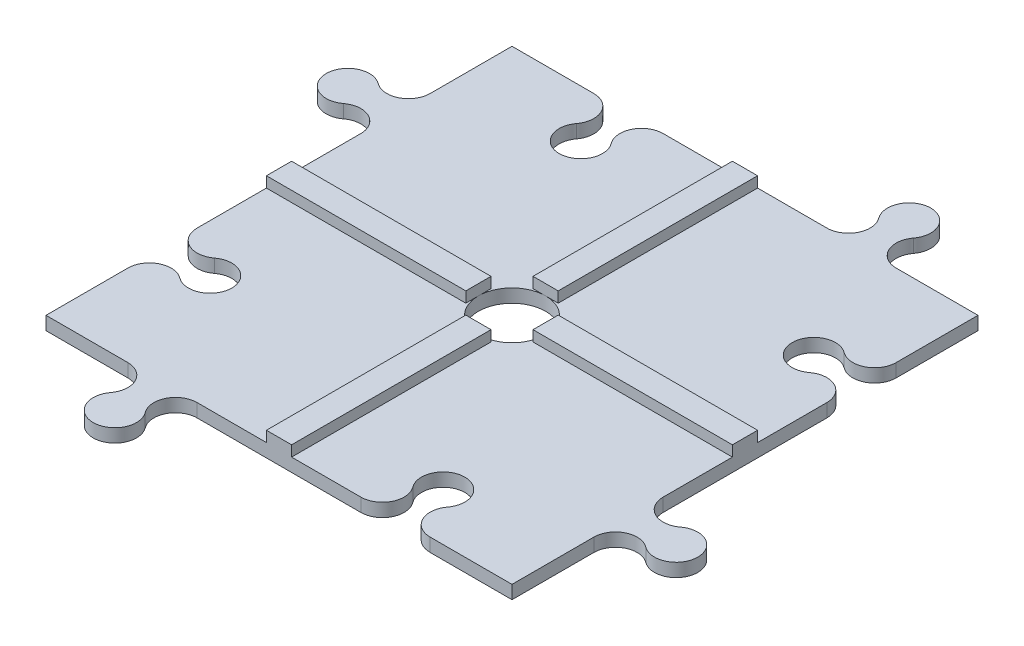
SolidWorks part; units mm, degrees
note: The reader was unsure of these and kept them because the rebuilt part matched: shared geometry of "Sketch2<3>".
ref_plane "Front Plane" through (0, 0, 0) normal (0, 0, 1) x (1, 0, 0)
ref_plane "Top Plane" through (0, 0, 0) normal (0, 1, 0) x (1, 0, 0)
ref_plane "Right Plane" through (0, 0, 0) normal (1, 0, 0) x (0, 0, -1)
sketch "Sketch1" plane through (0, 0, 0) normal (0, 1, 0) x (1, 0, 0)
  line L1 (55.5, -55.5) -> (-55.5, -55.5)
  line L2 (55.5, -55.5) -> (55.5, 55.5)
  line L3 (55.5, 55.5) -> (-55.5, 55.5)
  line L4 (-55.5, -55.5) -> (-55.5, 55.5)
  line L5 (55.5, -55.5) -> (-55.5, 55.5) construction
  line L6 (55.5, 55.5) -> (-55.5, -55.5) construction
  circle A0 centre (0, 0) radius 55.5 construction
  circle A1 centre (0, 0) radius 55.5 construction
  dimension "D1" = 111
extrude "Boss-Extrude1" add sketch "Sketch1" along normal blind 3.175 contours L4 L3 L2 L1
sketch "Sketch2" plane through (0, 0, 0) normal (0, 1, 0) x (1, 0, 0)
  line L0 (-55.5, 27.75) -> (-113.1129, 27.75) construction
  line L1 (-55.5, 36.005) -> (-55.5, 19.495)
  line L2 (-55.5, -55.5) -> (-55.5, 55.5) construction
  line L3 (0, 0) -> (-55.5, 0) construction
  line L4 (55.5, 55.5) -> (-55.5, -55.5) construction
  line L5 (-55.5, -36.005) -> (-55.5, -19.495)
  arc A0 (-63.755, 23.6225) -> (-72.01, 27.75) centre (-66.8506, 27.75) cw
  arc A1 (-63.755, 23.6225) -> (-55.5, 19.495) centre (-60.6594, 19.495) cw
  arc A2 (-63.755, 31.8775) -> (-55.5, 36.005) centre (-60.6594, 36.005) ccw
  arc A3 (-63.755, -23.6225) -> (-55.5, -19.495) centre (-60.6594, -19.495) ccw construction
  arc A4 (-63.755, 31.8775) -> (-72.01, 27.75) centre (-66.8506, 27.75) ccw
  arc A5 (-63.755, -23.6225) -> (-72.01, -27.75) centre (-66.8506, -27.75) ccw construction
  arc A6 (-63.755, -31.8775) -> (-72.01, -27.75) centre (-66.8506, -27.75) cw construction
  arc A7 (-63.755, -31.8775) -> (-55.5, -36.005) centre (-60.6594, -36.005) cw construction
  arc A8 (-47.245, -31.8775) -> (-55.5, -36.005) centre (-50.3406, -36.005) ccw
  arc A9 (-47.245, -31.8775) -> (-38.99, -27.75) centre (-44.1494, -27.75) ccw
  arc A10 (-47.245, -23.6225) -> (-38.99, -27.75) centre (-44.1494, -27.75) cw
  arc A11 (-47.245, -23.6225) -> (-55.5, -19.495) centre (-50.3406, -19.495) cw
  point P19 (-77.1865, 19.495)
  point P22 (-77.1865, 36.005)
  dimension "D1" = 16.51
  dimension "D2" = 16.51
extrude "Boss-Extrude2" add sketch "Sketch2" along normal up to surface (3.175 mm away) contours A0 A4 A2 L1 A1 up to face at (0, 3.175, 0)
extrude "Cut-Extrude2" cut sketch "Sketch2<3>" along normal through all contours L5 A11 A10 A9 A8
sketch "Sketch2<3>" plane through (0, 0, 0) normal (0, 1, 0) x (1, 0, 0) same geometry as "Sketch2"
sketch "Sketch3" [suppressed] plane through (0, 0, 0) normal (0, 0, 1) x (1, 0, 0)
  line L0 (0, 0) -> (0, 29.4045) construction
  line L1 (55.5, 0) -> (-55.5, 0) construction
pattern_circular "CirPattern1" count 4 over 360 about axis through (0, 0, 0) along (0, 1, 0) of "Boss-Extrude2", "Cut-Extrude2"
sketch "Sketch4" plane through (0, 3.175, 0) normal (0, 1, 0) x (1, 0, 0)
  circle A0 centre (0, 0) radius 8.001
  dimension "D1" = 16.002
extrude "Cut-Extrude3" cut sketch "Sketch4" against normal up to surface (3.175 mm away) up to face at (0, 0, 0)
sketch "Sketch5" plane through (0, 3.175, 0) normal (0, 1, 0) x (1, 0, 0)
  line L0 (-55.5, 3) -> (-7.4173, 3)
  line L1 (-55.5, -3) -> (-7.4173, -3)
  line L2 (-55.5, 55.5) -> (-55.5, -55.5)
  line L3 (-36.005, -55.5) -> (-55.5, -55.5) construction
  line L4 (-55.5, 0) -> (-8.001, 0) construction
  line L5 (-8.001, 3) -> (-8.001, -3)
  circle A0 centre (0, 0) radius 8.001 construction
  line M27 (-55.5, 19.495) -> (-55.5, -19.495)
  dimension "D1" = 6
extrude "Boss-Extrude3" add sketch "Sketch5" along normal blind 2.54 contours L4 L2 L1 L5 | L4 L5 L0 M27
pattern_circular "CirPattern2" count 4 over 360 about axis through (0, 0, 0) along (0, 1, 0) of "Boss-Extrude3"
sketch "Sketch6" plane through (0, 3.175, 0) normal (0, 1, 0) x (1, 0, 0)
  line L0 (0, 8.001) -> (-3, 8.001) construction
  line L1 (-3, 8.001) -> (-3, 55.5) construction
  line L2 (-3, 55.5) -> (-19.495, 55.5) construction
  line L3 (-36.005, 55.5) -> (-55.5, 55.5) construction
  line L4 (-55.5, 55.5) -> (-55.5, 36.005) construction
  line L5 (-55.5, 19.495) -> (-55.5, 3) construction
  line L6 (-55.5, 3) -> (-8.001, 3) construction
  line L7 (-8.001, 3) -> (-8.001, 0) construction
  line L8 (19.495, 55.5) -> (3, 55.5) construction
  line L9 (3, 55.5) -> (3, 8.001) construction
  line L10 (3, 8.001) -> (0, 8.001) construction
  line L11 (8.001, 0) -> (8.001, 3) construction
  line L12 (8.001, 3) -> (55.5, 3) construction
  line L13 (55.5, 3) -> (55.5, 19.495) construction
  line L14 (55.5, 36.005) -> (55.5, 55.5) construction
  line L15 (55.5, 55.5) -> (36.005, 55.5) construction
  line L16 (55.5, -19.495) -> (55.5, -3) construction
  line L17 (55.5, -3) -> (8.001, -3) construction
  line L18 (8.001, -3) -> (8.001, 0) construction
  line L19 (0, -8.001) -> (3, -8.001) construction
  line L20 (3, -8.001) -> (3, -55.5) construction
  line L21 (3, -55.5) -> (19.495, -55.5) construction
  line L22 (36.005, -55.5) -> (55.5, -55.5) construction
  line L23 (55.5, -55.5) -> (55.5, -36.005) construction
  line L24 (-19.495, -55.5) -> (-3, -55.5) construction
  line L25 (-3, -55.5) -> (-3, -8.001) construction
  line L26 (-3, -8.001) -> (0, -8.001) construction
  line L27 (-8.001, 0) -> (-8.001, -3) construction
  line L28 (-8.001, -3) -> (-55.5, -3) construction
  line L29 (-55.5, -3) -> (-55.5, -19.495) construction
  line L30 (-55.5, -36.005) -> (-55.5, -55.5) construction
  line L31 (-55.5, -55.5) -> (-36.005, -55.5) construction
  line L32 (0, 8.001) -> (-3, 8.001)
  line L33 (-3, 8.001) -> (-3, 55.5)
  line L34 (-3, 55.5) -> (-19.495, 55.5)
  line L35 (-36.005, 55.5) -> (-55.5, 55.5)
  line L36 (-55.5, 55.5) -> (-55.5, 36.005)
  line L37 (-55.5, 19.495) -> (-55.5, 3)
  line L38 (-55.5, 3) -> (-8.001, 3)
  line L39 (-8.001, 3) -> (-8.001, 0)
  line L40 (19.495, 55.5) -> (3, 55.5)
  line L41 (3, 55.5) -> (3, 8.001)
  line L42 (3, 8.001) -> (0, 8.001)
  line L43 (8.001, 0) -> (8.001, 3)
  line L44 (8.001, 3) -> (55.5, 3)
  line L45 (55.5, 3) -> (55.5, 19.495)
  line L46 (55.5, 36.005) -> (55.5, 55.5)
  line L47 (55.5, 55.5) -> (36.005, 55.5)
  line L48 (55.5, -19.495) -> (55.5, -3)
  line L49 (55.5, -3) -> (8.001, -3)
  line L50 (8.001, -3) -> (8.001, 0)
  line L51 (0, -8.001) -> (3, -8.001)
  line L52 (3, -8.001) -> (3, -55.5)
  line L53 (3, -55.5) -> (19.495, -55.5)
  line L54 (36.005, -55.5) -> (55.5, -55.5)
  line L55 (55.5, -55.5) -> (55.5, -36.005)
  line L56 (-19.495, -55.5) -> (-3, -55.5)
  line L57 (-3, -55.5) -> (-3, -8.001)
  line L58 (-3, -8.001) -> (0, -8.001)
  line L59 (-8.001, 0) -> (-8.001, -3)
  line L60 (-8.001, -3) -> (-55.5, -3)
  line L61 (-55.5, -3) -> (-55.5, -19.495)
  line L62 (-55.5, -36.005) -> (-55.5, -55.5)
  line L63 (-55.5, -55.5) -> (-36.005, -55.5)
  arc A1 (-19.495, 55.5) -> (-23.6225, 47.245) centre (-19.495, 50.3406) ccw construction
  arc A2 (-31.8775, 47.245) -> (-23.6225, 47.245) centre (-27.75, 44.1494) ccw construction
  arc A3 (-31.8775, 47.245) -> (-36.005, 55.5) centre (-36.005, 50.3406) ccw construction
  arc A4 (-63.755, 31.8775) -> (-55.5, 36.005) centre (-60.6594, 36.005) ccw construction
  arc A5 (-63.755, 31.8775) -> (-63.755, 23.6225) centre (-66.8506, 27.75) ccw construction
  arc A6 (-55.5, 19.495) -> (-63.755, 23.6225) centre (-60.6594, 19.495) ccw construction
  arc A8 (55.5, 19.495) -> (47.245, 23.6225) centre (50.3406, 19.495) ccw construction
  arc A9 (47.245, 31.8775) -> (47.245, 23.6225) centre (44.1494, 27.75) ccw construction
  arc A10 (47.245, 31.8775) -> (55.5, 36.005) centre (50.3406, 36.005) ccw construction
  arc A11 (31.8775, 63.755) -> (36.005, 55.5) centre (36.005, 60.6594) ccw construction
  arc A12 (31.8775, 63.755) -> (23.6225, 63.755) centre (27.75, 66.8506) ccw construction
  arc A13 (19.495, 55.5) -> (23.6225, 63.755) centre (19.495, 60.6594) ccw construction
  arc A15 (19.495, -55.5) -> (23.6225, -47.245) centre (19.495, -50.3406) ccw construction
  arc A16 (31.8775, -47.245) -> (23.6225, -47.245) centre (27.75, -44.1494) ccw construction
  arc A17 (31.8775, -47.245) -> (36.005, -55.5) centre (36.005, -50.3406) ccw construction
  arc A18 (63.755, -31.8775) -> (55.5, -36.005) centre (60.6594, -36.005) ccw construction
  arc A19 (63.755, -31.8775) -> (63.755, -23.6225) centre (66.8506, -27.75) ccw construction
  arc A20 (55.5, -19.495) -> (63.755, -23.6225) centre (60.6594, -19.495) ccw construction
  arc A22 (-55.5, -19.495) -> (-47.245, -23.6225) centre (-50.3406, -19.495) ccw construction
  arc A23 (-47.245, -31.8775) -> (-47.245, -23.6225) centre (-44.1494, -27.75) ccw construction
  arc A24 (-47.245, -31.8775) -> (-55.5, -36.005) centre (-50.3406, -36.005) ccw construction
  arc A25 (-31.8775, -63.755) -> (-36.005, -55.5) centre (-36.005, -60.6594) ccw construction
  arc A26 (-31.8775, -63.755) -> (-23.6225, -63.755) centre (-27.75, -66.8506) ccw construction
  arc A27 (-19.495, -55.5) -> (-23.6225, -63.755) centre (-19.495, -60.6594) ccw construction
  arc A29 (-19.495, 55.5) -> (-23.6225, 47.245) centre (-19.495, 50.3406) ccw
  arc A30 (-31.8775, 47.245) -> (-23.6225, 47.245) centre (-27.75, 44.1494) ccw
  arc A31 (-31.8775, 47.245) -> (-36.005, 55.5) centre (-36.005, 50.3406) ccw
  arc A32 (-63.755, 31.8775) -> (-55.5, 36.005) centre (-60.6594, 36.005) ccw
  arc A33 (-63.755, 31.8775) -> (-63.755, 23.6225) centre (-66.8506, 27.75) ccw
  arc A34 (-55.5, 19.495) -> (-63.755, 23.6225) centre (-60.6594, 19.495) ccw
  arc A36 (55.5, 19.495) -> (47.245, 23.6225) centre (50.3406, 19.495) ccw
  arc A37 (47.245, 31.8775) -> (47.245, 23.6225) centre (44.1494, 27.75) ccw
  arc A38 (47.245, 31.8775) -> (55.5, 36.005) centre (50.3406, 36.005) ccw
  arc A39 (31.8775, 63.755) -> (36.005, 55.5) centre (36.005, 60.6594) ccw
  arc A40 (31.8775, 63.755) -> (23.6225, 63.755) centre (27.75, 66.8506) ccw
  arc A41 (19.495, 55.5) -> (23.6225, 63.755) centre (19.495, 60.6594) ccw
  arc A43 (19.495, -55.5) -> (23.6225, -47.245) centre (19.495, -50.3406) ccw
  arc A44 (31.8775, -47.245) -> (23.6225, -47.245) centre (27.75, -44.1494) ccw
  arc A45 (31.8775, -47.245) -> (36.005, -55.5) centre (36.005, -50.3406) ccw
  arc A46 (63.755, -31.8775) -> (55.5, -36.005) centre (60.6594, -36.005) ccw
  arc A47 (63.755, -31.8775) -> (63.755, -23.6225) centre (66.8506, -27.75) ccw
  arc A48 (55.5, -19.495) -> (63.755, -23.6225) centre (60.6594, -19.495) ccw
  arc A50 (-55.5, -19.495) -> (-47.245, -23.6225) centre (-50.3406, -19.495) ccw
  arc A51 (-47.245, -31.8775) -> (-47.245, -23.6225) centre (-44.1494, -27.75) ccw
  arc A52 (-47.245, -31.8775) -> (-55.5, -36.005) centre (-50.3406, -36.005) ccw
  arc A53 (-31.8775, -63.755) -> (-36.005, -55.5) centre (-36.005, -60.6594) ccw
  arc A54 (-31.8775, -63.755) -> (-23.6225, -63.755) centre (-27.75, -66.8506) ccw
  arc A55 (-19.495, -55.5) -> (-23.6225, -63.755) centre (-19.495, -60.6594) ccw
sketch "Sketch7" plane through (0, 3.175, 0) normal (0, 1, 0) x (1, 0, 0)
  line L4 (-8.001, -3) -> (-8.001, 3)
  line L5 (-8.001, 3) -> (-55.5, 3)
  line L6 (-55.5, 3) -> (-55.5, -3)
  line L7 (-55.5, -3) -> (-8.001, -3)
  line L8 (-8.001, -3) -> (-8.001, 3)
  line L9 (-8.001, 3) -> (-55.5, 3)
  line L10 (-55.5, 3) -> (-55.5, -3)
  line L11 (-55.5, -3) -> (-8.001, -3)
  dimension "D1" = 0
